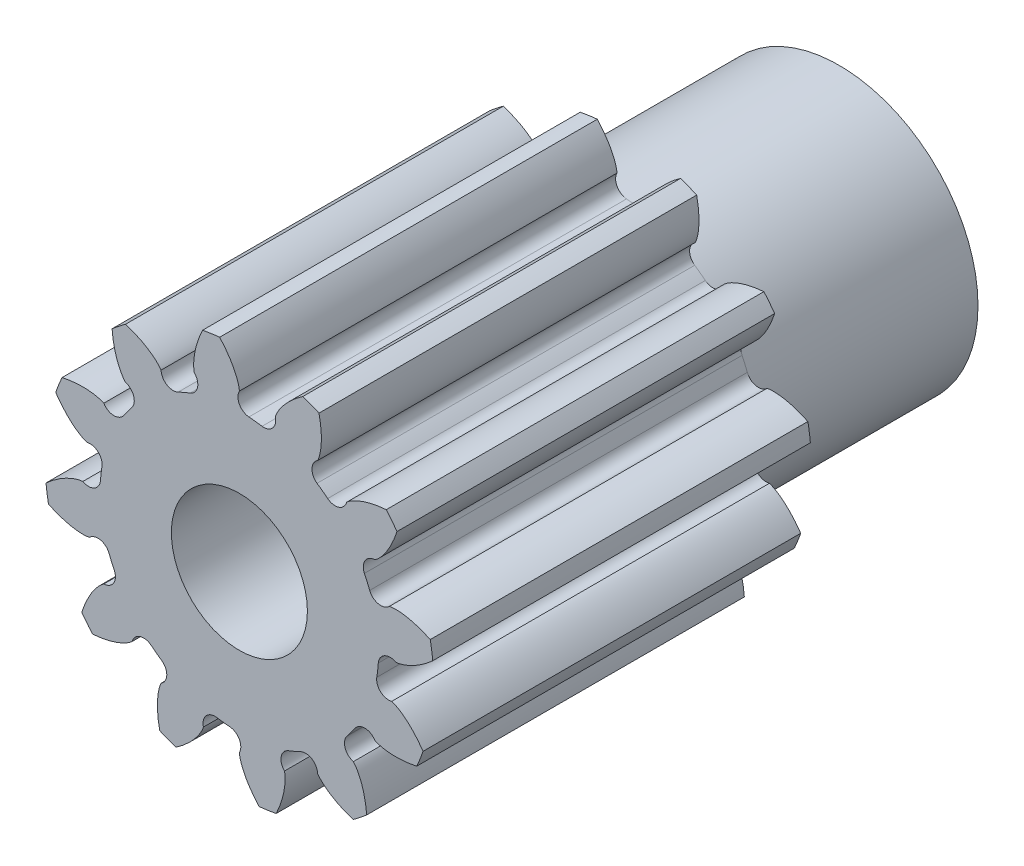
SolidWorks part; units mm, degrees
ref_plane "Front Plane" through (0, 0, 0) normal (0, 0, 1) x (1, 0, 0)
ref_plane "Top Plane" through (0, 0, 0) normal (0, 1, 0) x (1, 0, 0)
ref_plane "Right Plane" through (0, 0, 0) normal (1, 0, 0) x (0, 0, -1)
sketch "Sketch2" plane through (0, 0, 0) normal (0, 0, 1) x (1, 0, 0)
  spline S0 degree 4 poles (2.8191, 0) (2.8227, 0.0001) (2.8295, 0.0005) (2.8406, 0.0016) (2.8624, 0.0048) (2.8869, 0.0097) (2.9143, 0.0165) (2.9436, 0.0251) (2.9685, 0.0333) (2.9931, 0.0421) (3.0175, 0.0516) (3.0469, 0.0638) (3.0818, 0.0795) (3.1221, 0.0994) (3.1672, 0.1238) (3.2125, 0.1505) (3.2564, 0.1783) (3.3001, 0.2081) (3.3418, 0.2383) (3.3843, 0.2713) (3.4231, 0.3027) (3.4657, 0.3397) (3.4997, 0.3701) (3.5435, 0.4122) (3.569, 0.4377) (3.5985, 0.4681) (3.6114, 0.482) (3.6194, 0.4905) knots 0 0 0 0 0 0.015084 0.028532 0.04661 0.092111 0.119476 0.146842 0.174209 0.201575 0.228941 0.256307 0.307035 0.361767 0.4165 0.471232 0.525964 0.580697 0.635429 0.690161 0.744894 0.799626 0.854358 0.909091 0.954545 1 1 1 1 1 construction
  spline S1 degree 4 poles (2.8191, 0) (2.8227, 0.0001) (2.8295, 0.0005) (2.8406, 0.0016) (2.8624, 0.0048) (2.8869, 0.0097) (2.9143, 0.0165) (2.9436, 0.0251) (2.9685, 0.0333) (2.9931, 0.0421) (3.0175, 0.0516) (3.0469, 0.0638) (3.0818, 0.0795) (3.1221, 0.0994) (3.1672, 0.1238) (3.2125, 0.1505) (3.2564, 0.1783) (3.3001, 0.2081) (3.3418, 0.2383) (3.3843, 0.2713) (3.4231, 0.3027) (3.4657, 0.3397) (3.4997, 0.3701) (3.534, 0.4031) (3.5506, 0.4194) (3.559, 0.4278) knots 0 0 0 0 0 0.015084 0.028532 0.04661 0.092111 0.119476 0.146842 0.174209 0.201575 0.228941 0.256307 0.307035 0.361767 0.4165 0.471232 0.525964 0.580697 0.635429 0.690161 0.744894 0.799626 0.854358 0.909091 0.909091 0.909091 0.909091 0.909091
sketch "Sketch3" plane through (0, 0, 0) normal (0, 0, 1) x (1, 0, 0)
  line L0 (0.0245, 0) -> (50000.0245, 0) construction
  line L2 (0.0501, 0.0074) -> (49467.8988, 7274.3245) construction
  circle A0 centre (0, 0) radius 2.375 construction
  circle A1 centre (0, 0) radius 3 construction
  circle A2 centre (0, 0) radius 3.5
  circle A3 centre (0, 0) radius 2.5071
  arc A4 (2.8191, 0) -> (2.5012, -0.1711) centre (2.7168, -0.1908) ccw
  arc A5 (2.6997, 0.8115) -> (2.3461, 0.8839) centre (2.5469, 0.9648) cw
  spline S0 degree 4 poles (2.6997, 0.8115) (2.7032, 0.8125) (2.7099, 0.8141) (2.7208, 0.8162) (2.7426, 0.8194) (2.7675, 0.8218) (2.7957, 0.8231) (2.8262, 0.8233) (2.8524, 0.8227) (2.8786, 0.8213) (2.9046, 0.8193) (2.9363, 0.816) (2.9742, 0.811) (3.0185, 0.8036) (3.0687, 0.7932) (3.1198, 0.7807) (3.1699, 0.7667) (3.2203, 0.7507) (3.2689, 0.7339) (3.3191, 0.7145) (3.3651, 0.6957) (3.4033, 0.6784) (3.4255, 0.6682) (3.4366, 0.6629) knots 0 0 0 0 0 0.015084 0.028532 0.04661 0.092111 0.119476 0.146842 0.174209 0.201575 0.228941 0.256307 0.307035 0.361767 0.4165 0.471232 0.525964 0.580697 0.635429 0.690161 0.744894 0.798429 0.798429 0.798429 0.798429 0.798429
  spline S1 degree 4 poles (2.2653, 999.9963) (2.185, 1.5975) (2.4278, 0.1065) (2.6495, -0.0262) (2.8624, 0.0048) (2.8869, 0.0097) (2.9143, 0.0165) (2.9436, 0.0251) (2.9685, 0.0333) (2.9931, 0.0421) (3.0175, 0.0516) (3.0469, 0.0638) (3.0818, 0.0795) (3.1221, 0.0994) (3.1672, 0.1238) (3.2125, 0.1505) (3.2564, 0.1783) (3.3001, 0.2081) (3.3418, 0.2383) (3.3843, 0.2713) (3.4231, 0.3027) (3.4657, 0.3397) (3.6828, 0.5338) (4.4773, 1.398) (-10.7975, -13.7561) (710.4834, 707.7059) knots -0.807508 -0.807508 -0.807508 -0.807508 -0.807508 0.015084 0.028532 0.04661 0.092111 0.119476 0.146842 0.174209 0.201575 0.228941 0.256307 0.307035 0.361767 0.4165 0.471232 0.525964 0.580697 0.635429 0.690161 0.744894 0.799626 0.854358 2.086489 2.086489 2.086489 2.086489 2.086489 only from (2.8191, 0) to (3.559, 0.4278) construction
  spline S3 degree 4 poles (2.8191, 0) (2.8227, 0.0001) (2.8295, 0.0005) (2.8406, 0.0016) (2.8624, 0.0048) (2.8869, 0.0097) (2.9143, 0.0165) (2.9436, 0.0251) (2.9685, 0.0333) (2.9931, 0.0421) (3.0175, 0.0516) (3.0469, 0.0638) (3.0818, 0.0795) (3.1221, 0.0994) (3.1672, 0.1238) (3.2125, 0.1505) (3.2564, 0.1783) (3.3001, 0.2081) (3.3418, 0.2383) (3.3843, 0.2713) (3.4229, 0.3025) (3.4546, 0.33) (3.4729, 0.3462) (3.482, 0.3545) knots 0 0 0 0 0 0.015084 0.028532 0.04661 0.092111 0.119476 0.146842 0.174209 0.201575 0.228941 0.256307 0.307035 0.361767 0.4165 0.471232 0.525964 0.580697 0.635429 0.690161 0.744894 0.798429 0.798429 0.798429 0.798429 0.798429
  point P10 (2.9681, 0.4365)
  point P15 (2.9997, 0.0447)
  dimension "D2" = 6
  dimension "D3" = 7
  dimension "D4" = 4.75
  dimension "D1" = 0.3933
extrude "Boss-Extrude1" add sketch "Sketch3" along normal blind 6.8 contours A3 region at (0, 0, 0)
extrude "Boss-Extrude2" add sketch "Sketch3<3>" along normal blind 6.8 contours A4 S3 A2 S0 A5 A3 region at (2.9113, 0.4281, 0)
sketch "Sketch3<3>" plane through (0, 0, 0) normal (0, 0, 1) x (1, 0, 0) same geometry as "Sketch3"
pattern_circular "CirPattern1" count 12 over 360 about axis through (0, 0, 6.8) along (0, 0, -1) of "Boss-Extrude2"
sketch "Sketch4" plane through (0, 0, 6.8) normal (0, 0, 1) x (1, 0, 0)
  circle A0 centre (0, 0) radius 1.225
  dimension "D1" = 2.45
extrude "Cut-Extrude1" cut sketch "Sketch4" against normal blind 6.8
sketch "Sketch5" plane through (0, 0, 0) normal (0, 0, -1) x (-1, 0, 0)
  circle A0 centre (0, 0) radius 1.225 construction
  circle A1 centre (0, 0) radius 1.225
  circle A2 centre (0, 0) radius 2.5
  dimension "D1" = 5
extrude "Boss-Extrude3" add sketch "Sketch5" along normal blind 4
sketch "Sketch6" plane through (0, 0, 6.8) normal (0, 0, 1) x (1, 0, 0)
  circle A0 centre (0, 0) radius 3 construction
  circle A1 centre (0, 0) radius 3 construction
equation "\"m\"= 22.5 / 45mm'module"
equation "\"N\"= 12'number of teeth"
equation "\"a\"= 20deg'pressure angle"
equation "\"da\"= \"m\" * ( \"N\" + 2 )'addendum circle diameter"
equation "\"df\"= \"m\" * ( \"N\" - 2.5 )'dedendum circle diameter"
equation "\"db\"= \"m\" * \"N\" * cos ( \"a\" )'basic circle diameter"
equation "\"rb\"= \"db\" / 2'basic circle radius"
equation "\"s\"= \"m\" * pi / 2'pitch circle tooth thickness"
equation "\"r\"= \"m\" * 0.38'dedendum circle angle"
equation "\"B\"= \"d\" * 0.3'tooth width"
equation "\"d\"= 6mm"
equation "\"D2@Sketch3\"=\"d\""
equation "\"D4@Sketch3\"=\"df\""
